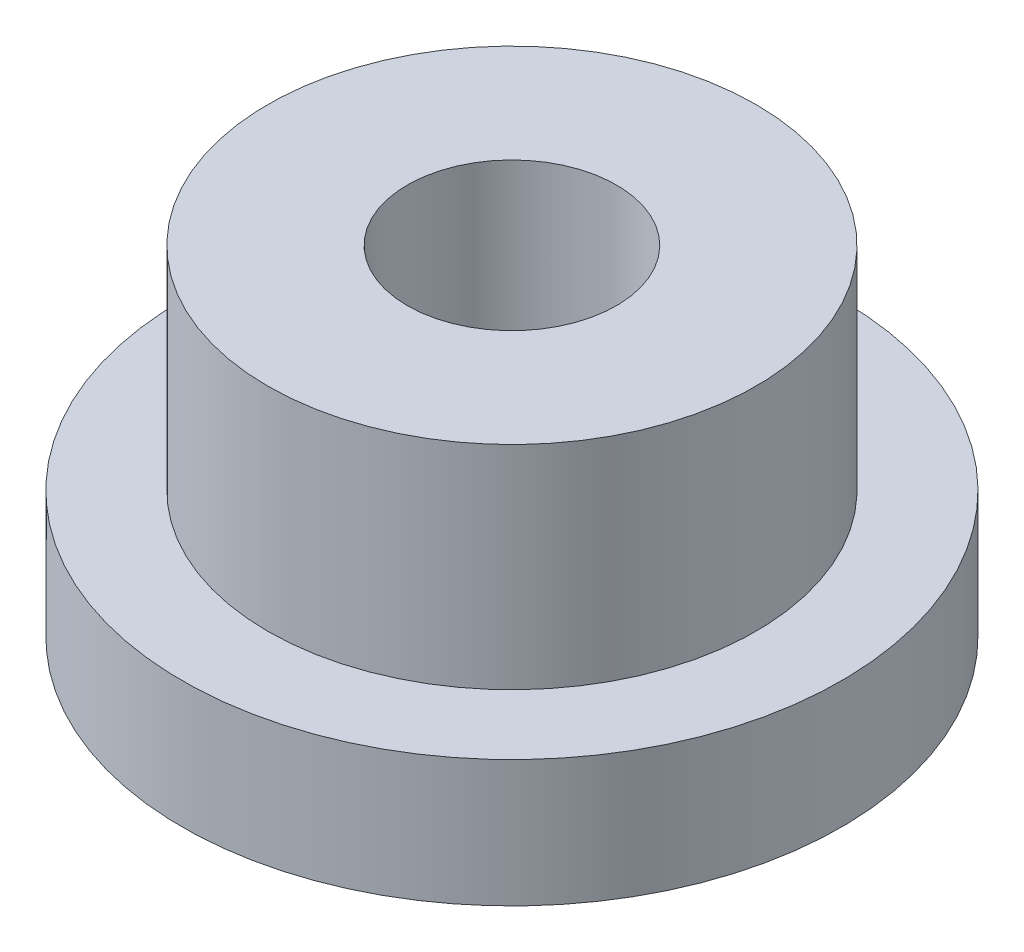
SolidWorks part; units mm, degrees
ref_plane "前视基准面" through (0, 0, 0) normal (0, 0, 1) x (1, 0, 0)
ref_plane "上视基准面" through (0, 0, 0) normal (0, 1, 0) x (1, 0, 0)
ref_plane "右视基准面" through (0, 0, 0) normal (1, 0, 0) x (0, 0, -1)
other "Configuration Table"
sketch "草图2" plane through (0, 0, 0) normal (0, 1, 0) x (1, 0, 0)
  circle A0 centre (0, 0) radius 1.65
  circle A1 centre (0, 0) radius 3.85
  dimension "D1" = 3.3
  dimension "D2" = 7.7
extrude "凸台-拉伸8" add sketch "草图2" against normal blind 3.35
ref_plane "基准面1" through (0, -3.35, 0) normal (0, -1, 0) x (-1, 0, 0)
sketch "草图3" plane through (0, -3.35, 0) normal (0, -1, 0) x (-1, 0, 0)
  circle A0 centre (0, 0) radius 5.2
  circle A2 centre (0, 0) radius 3.85
  dimension "D1" = 10.4
  dimension "D2" = 7.7
extrude "凸台-拉伸9" add sketch "草图3" along normal blind 2 contours A0
ref_plane "基准面2" through (0, -5.35, 0) normal (0, -1, 0) x (-1, 0, 0)
sketch "草图8" plane through (0, -5.35, 0) normal (0, -1, 0) x (-1, 0, 0)
  circle A1 centre (0, 0) radius 3.65
  dimension "D1" = 7.3
sketch "草图9" plane through (0, -3.35, 0) normal (0, -1, 0) x (-1, 0, 0)
  circle A0 centre (0, 0) radius 1.65
  dimension "D1" = 3.3
loft "切除-放样1" cut profiles "草图8", "草图9" connector at (0.7649, -5.35, -3.569) connector at (-0.5354, -3.35, -1.5607)
